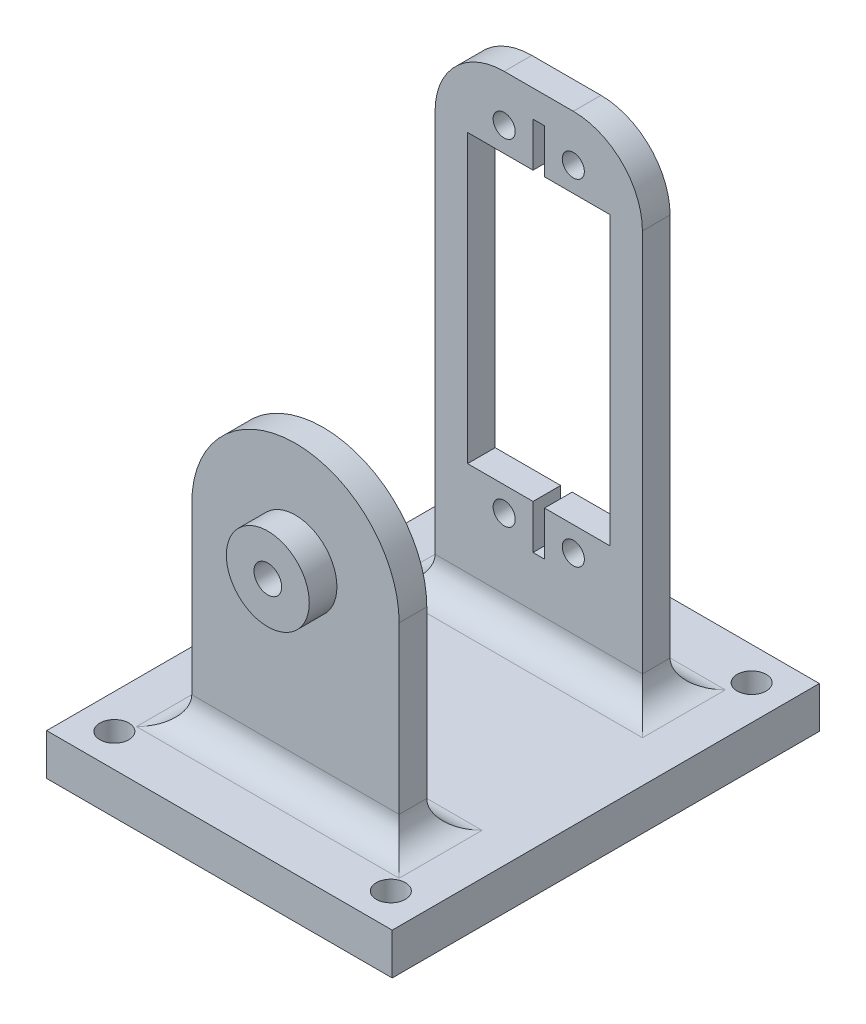
SolidWorks part; units mm, degrees
ref_plane "Front Plane" through (0, 0, 0) normal (0, 0, 1) x (1, 0, 0)
ref_plane "Top Plane" through (0, 0, 0) normal (0, 1, 0) x (1, 0, 0)
ref_plane "Right Plane" through (0, 0, 0) normal (1, 0, 0) x (0, 0, -1)
sketch "Sketch1" plane through (0, 0, 0) normal (0, 0, 1) x (1, 0, 0)
  line L0 (0, 0) -> (0, 53.2406) construction
  line L5 (-15, -28) -> (15, -28)
  line L6 (-15, -28) -> (-15, 31.5)
  line L7 (-5, 41.5) -> (5, 41.5)
  line L8 (15, -28) -> (15, 31.5)
  line L9 (0, 0) -> (15, 0) construction
  line L10 (-10.3, -10.3) -> (-0.83, -10.3)
  line L11 (-10.3, -10.3) -> (-10.3, 31.2)
  line L12 (-10.3, 31.2) -> (-0.83, 31.2)
  line L13 (10.3, -10.3) -> (10.3, 31.2)
  line L15 (-0.83, 31.2) -> (-0.83, 37.6)
  line L16 (-0.83, 37.6) -> (0.83, 37.6)
  line L17 (0.83, 31.2) -> (0.83, 37.6)
  line L18 (-10.3, 10.45) -> (10.3, 10.45) construction
  line L19 (-0.83, -10.3) -> (-0.83, -16.7)
  line L20 (-0.83, -16.7) -> (0.83, -16.7)
  line L21 (0.83, -10.3) -> (0.83, -16.7)
  line L22 (0.83, -10.3) -> (10.3, -10.3)
  line L23 (0.83, 31.2) -> (10.3, 31.2)
  arc A0 (5, 41.5) -> (15, 31.5) centre (5, 31.5) cw
  arc A1 (-15, 31.5) -> (-5, 41.5) centre (-5, 31.5) cw
  circle A2 centre (-5, 34.75) radius 1.6
  circle A3 centre (-5, -13.85) radius 1.6
  circle A4 centre (5, 34.75) radius 1.6
  circle A5 centre (5, -13.85) radius 1.6
  dimension "D4" = 10
  dimension "D10" = 3.2
  dimension "D13" = 3.2
  dimension "D1" = 30
  dimension "D2" = 41.5
  dimension "D3" = 28
  dimension "D5" = 20.6
  dimension "D6" = 31.2
  dimension "D7" = 10.3
  dimension "D8" = 5
  dimension "D9" = 34.75
  dimension "D11" = 5
  dimension "D12" = 13.85
  dimension "D14" = 37.6
  dimension "D15" = 1.66
extrude "Boss-Extrude1" add sketch "Sketch1" along normal blind 4
ref_plane "Plane1" through (0, 0, 39.2) normal (0, 0, 1) x (1, 0, 0)
sketch "Sketch2" plane through (0, 0, 39.2) normal (0, 0, 1) x (1, 0, 0)
  line L0 (0, 0) -> (0, 30.7043) construction
  line L1 (-15, -28) -> (15, -28)
  line L2 (-15, -28) -> (-15, 0)
  line L4 (15, -28) -> (15, 0)
  arc A0 (-15, 0) -> (15, 0) centre (0, 0) cw
  dimension "D3" = 15
  dimension "D1" = 30
  dimension "D2" = 28
extrude "Boss-Extrude2" add sketch "Sketch2" against normal blind 4 separate body
sketch "Sketch3" plane through (0, 0, 39.2) normal (0, 0, 1) x (1, 0, 0)
  circle A0 centre (0, 0) radius 6
  dimension "D1" = 12
extrude "Boss-Extrude3" add sketch "Sketch3" along normal blind 4
sketch "Sketch4" plane through (0, 0, 43.2) normal (0, 0, 1) x (1, 0, 0)
  circle A0 centre (0, 0) radius 2
  dimension "D1" = 4
extrude "Cut-Extrude1" cut sketch "Sketch4" against normal through all
ref_plane "Plane2" through (0, -28, 0) normal (0, 1, 0) x (1, 0, 0)
sketch "Sketch5" plane through (0, -28, 0) normal (0, 1, 0) x (1, 0, 0)
  line L0 (0, 0) -> (0, -51.9066) construction
  line L1 (-25, 11.6) -> (25, 11.6)
  line L2 (-25, 11.6) -> (-25, -50.2)
  line L3 (-25, -50.2) -> (25, -50.2)
  line L4 (25, 11.6) -> (25, -50.2)
  line L5 (-15, 0) -> (15, 0) construction
  line L7 (-16.5, -39.2) -> (16.5, -39.2) construction
  dimension "D2" = 11.6
  dimension "D1" = 50
  dimension "D3" = 11
  dimension "D4" = 61.8
extrude "Boss-Extrude4" add sketch "Sketch5" against normal blind 6
sketch "Sketch6" plane through (0, -34, 0) normal (0, -1, 0) x (1, 0, 0)
  line L0 (-25, 19.3) -> (25, 19.3) construction
  line L1 (-25, -11.6) -> (-25, 50.2) construction
  line L2 (25, 50.2) -> (25, -11.6) construction
  line L3 (0, 50.2) -> (0, -11.6) construction
  line L4 (-25, 50.2) -> (25, 50.2) construction
  line L5 (25, -11.6) -> (-25, -11.6) construction
  circle A0 centre (-20, 45.4) radius 2.1
  circle A1 centre (20, 45.4) radius 2.1
  circle A2 centre (20, -6.8) radius 2.1
  circle A3 centre (-20, -6.8) radius 2.1
  dimension "D1" = 4.2
  dimension "D2" = 20
  dimension "D3" = 45.4
extrude "Cut-Extrude2" cut sketch "Sketch6" against normal up to surface (6 mm away) up to face at (0, -28, 2)
fillet "Fillet1" radius 4 8 edges at (0, -28, 39.2) (-15, -28, 37.2) (15, -28, 37.2) (0, -28, 35.2) (15, -28, 2) (0, -28, 4) (-15, -28, 2) (0, -28, 0)
equation "\"L1\"= 120mm'Upper arm"
equation "\"L3\"= 75mm'Wrist→TCP"
equation "\"h0\"= 75mm'Shoulder height"
equation "\"t_link\"= 3mm'Link plate thickness"
equation "\"t_bracket\"= 4mm'Bracket thickness"
equation "\"d_pin\"= 4mm'Pin diameter (M4)"
equation "\"c_fit\"= 0.2mm'Nominal clearance - measured PLA 2026-10-01"
equation "\"L2\"= 120mm'Forearm"
equation "\"c_fit_pivot\"= \"c_fit\" + 0.05mm'Gripper pivot clearance - chosen 0.25 mm 2026-10-01"
equation "\"d_pin_gripper\"= 3mm'Gripper pivot diameter"
equation "\"w_link\"= 20mm'Link plate depth (bending direction)"
equation "\"w_gap\"= 20mm'Twin-plate gap - provisional, set by elbow servo mount"
equation "\"d_boss\"= 13mm'MG996R output boss dia - from downloaded model, verify with calipers"
equation "\"c_boss\"= 1mm'Radial clearance around servo boss"
equation "\"d_servo_hole\"= \"d_boss\" + 2 * \"c_boss\"'Plate clearance hole for servo boss (15 mm)"
equation "\"t_rim\"= 9.5mm'Min material around servo hole (M3 hole + 3 mm webs each side)"
equation "\"w_link_end\"= \"d_servo_hole\" + 2 * \"t_rim\"'Link plate end width at servo end (34 mm)"
equation "\"d_hole_m3\"= \"d_pin_gripper\" + \"c_fit\"'M3 bolt clearance hole (spacer and adapter bolts)"
equation "\"d_hole_pivot\"= \"d_pin\" + \"c_fit_pivot\"'M4 pivot hole where the pin rotates (4.25 mm)"
equation "\"d_horn\"= 20mm'Horn disc diameter (circular horn) - from MG996R model"
equation "\"t_horn\"= 2.3mm'Horn disc thickness"
equation "\"g_horn\"= 2.2mm'Gap from horn disc to plate 2 inner face - from MockShoulder"
equation "\"d_horn_pocket\"= \"d_horn\" + \"c_fit\"'Adapter pocket for horn disc (20.2 mm)"
equation "\"h_horn_pocket\"= \"g_horn\" + \"t_horn\"'Pocket depth from adapter plate-2 face (4.5 mm)"
equation "\"d_horn_screw_cb\"= 8.5mm'Recess for horn centre-screw head (head is 7.5 mm)"
equation "\"h_horn_screw_cb\"= 2.6mm'Recess depth (head is 2.35 mm tall)"
equation "\"d_adapter\"= 26mm'Horn adapter outer diameter"
equation "\"h_adapter\"= \"w_gap\"'Adapter length, fills the plate gap"
equation "\"t_adapter_floor\"= 2mm'Floor under horn disc that the horn screws pass through"
equation "\"d_horn_screw_hole\"= 2.2mm'Clearance for M2 self-tapper through the floor"
equation "\"r_horn_screw\"= 7mm'Horn screw hole radius (14 mm square pattern)"
equation "\"d_access\"= 4mm'Access bore for the M2 screws from the plate-1 side"
equation "\"d_insert_m3\"= 4.2mm'Hole for M3 heat-set insert - check the insert maker spec"
equation "\"h_insert_m3\"= 6mm'Insert hole depth"
equation "\"x_adapter_bolt\"= 6mm'Adapter bolt offset from pin, along the arm toward its middle"
equation "\"y_adapter_bolt\"= 5mm'Adapter bolt offset from pin, across the arm (+/-)"
equation "\"d_csk_m3\"= 6.4mm'Countersink diameter in plate 1 for M3 flat head (90 deg)"
equation "\"h_pin_bore\"= 10mm'M4 pin engagement depth in the adapter"
equation "\"c_win\"= 0.3mm'Servo window clearance per side in bracket wall A - starting value, tune after a test print"
equation "\"l_servo\"= 40.9mm'MG996R case length without ears - from the model"
equation "\"w_servo\"= 20mm'MG996R case width - from the model"
equation "\"r_servo_short\"= 10mm'Shaft axis to the short end of the case - from the model"
equation "\"r_servo_long\"= \"l_servo\" - \"r_servo_short\"'Shaft axis to the long end of the case (30.9 mm)"
equation "\"l_ear_holes\"= 48.6mm'MG996R ear hole (keyhole slot) spacing along the case - from the model"
equation "\"w_ear_holes\"= 10mm'MG996R ear hole spacing across the case - from the model"
equation "\"a_ear\"= 8.2mm'Servo ear seating face to plate-2 outer face - from MockShoulder (ear face incl. 0.2 edge round)"
equation "\"l_window\"= \"l_servo\" + 2 * \"c_win\"'Wall A window length (41.5 mm)"
equation "\"w_window\"= \"w_servo\" + 2 * \"c_win\"'Wall A window width (20.6 mm)"
equation "\"g_wall_a\"= \"a_ear\" - \"t_bracket\"'Gap behind wall A to plate 2 (4.4 mm) - ear screw heads sit here"
equation "\"g_wall_b\"= 1mm'Plate 1 outer face to wall B - thrust washer"
equation "\"d_axis_turret\"= 34mm'Shoulder axis to turret mounting face - PLACEHOLDER until the turret is designed"
equation "\"t_foot\"= 6mm'Bracket foot thickness"
equation "\"h_wall_top\"= 41.5mm'Wall A top above the shoulder axis (long-end ear holes + 4 mm)"
equation "\"w_wall\"= 30mm'Bracket wall A and B width"
equation "\"w_foot\"= 50mm'Bracket foot width across the walls"
equation "\"t_boss_b\"= 4mm'Extra thickness of the pin boss on the outside of wall B"
equation "\"d_boss_b\"= 12mm'Pin boss diameter on wall B"
equation "\"D1@Sketch1\"=\"w_wall\""
equation "\"D2@Sketch1\"=\"h_wall_top\""
equation "\"D3@Sketch1\"=\"d_axis_turret\" - \"t_foot\""
equation "\"D5@Sketch1\"=\"w_window\""
equation "\"D6@Sketch1\"=\"r_servo_long\" + \"c_win\""
equation "\"D7@Sketch1\"=\"r_servo_short\" + \"c_win\""
equation "\"D8@Sketch1\"=\"w_ear_holes\"/2"
equation "\"D9@Sketch1\"=\"l_ear_holes\"/2 + \"l_servo\"/2 - \"r_servo_short\""
equation "\"D10@Sketch1\"=\"d_hole_m3\""
equation "\"D11@Sketch1\"=\"w_ear_holes\"/2"
equation "\"D12@Sketch1\"=\"l_ear_holes\"/2 - (\"l_servo\"/2 - \"r_servo_short\")"
equation "\"D13@Sketch1\"=\"d_hole_m3\""
equation "\"D1@Boss-Extrude1\"=\"t_bracket\""
equation "\"D1@Sketch3\"=\"d_boss_b\""
equation "\"D1@Boss-Extrude3\"=\"t_boss_b\""
equation "\"D1@Sketch4\"=\"d_pin\""
equation "\"D1@Sketch5\"=\"w_foot\""
equation "\"D1@Boss-Extrude4\"=\"t_foot\""
equation "\"D1@Sketch6\"=\"d_insert_m3\""
